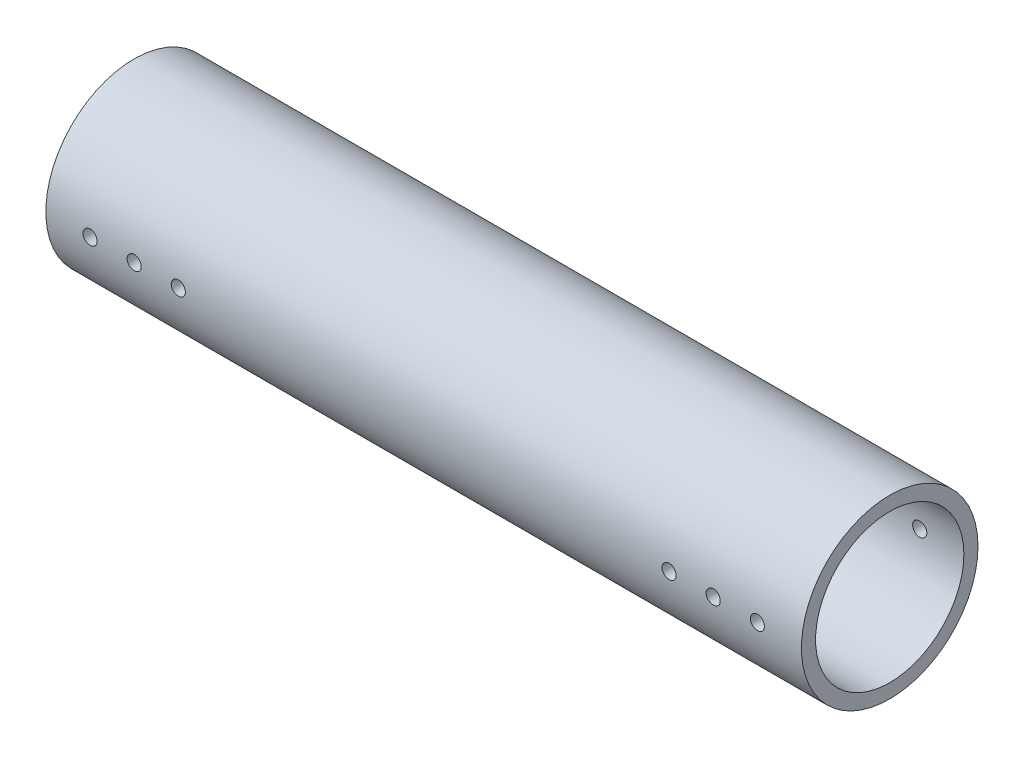
SolidWorks part; units mm, degrees
material "Zoltek Panex 33"
ref_plane "Спереди" through (0, 0, 0) normal (0, 0, 1) x (1, 0, 0)
ref_plane "Сверху" through (0, 0, 0) normal (0, 1, 0) x (1, 0, 0)
ref_plane "Справа" through (0, 0, 0) normal (1, 0, 0) x (0, 0, -1)
other "Configuration Table"
sketch "Эскиз2" plane through (0, 0, 0) normal (1, 0, 0) x (0, 0, -1)
  circle A0 centre (0, 0) radius 25
  circle A1 centre (0, 0) radius 21
  dimension "D1" = 50
  dimension "D2" = 42
extrude "Бобышка-Вытянуть2" add sketch "Эскиз2" along normal blind 214
ref_plane "Плоскость1" through (0, 0, 25) normal (0, 0, 1) x (1, 0, 0)
sketch "Эскиз4" plane through (0, 0, 25) normal (0, 0, 1) x (1, 0, 0)
  line L0 (0, -25) -> (214, -25) construction
  line L1 (214, -25) -> (214, 25) construction
  circle A0 centre (12.5, 0) radius 2
  circle A1 centre (201.5, 0) radius 2
  circle A2 centre (25, 0) radius 2
  circle A3 centre (37.5, 0) radius 2
  circle A4 centre (189, 0) radius 2
  circle A5 centre (176.5, 0) radius 2
  dimension "D1" = 4
  dimension "D4" = 4
  dimension "D6" = 4
  dimension "D8" = 4
  dimension "D10" = 4
  dimension "D11" = 4
  dimension "D2" = 12.5
  dimension "D3" = 25
  dimension "D5" = 12.5
  dimension "D7" = 12.5
  dimension "D9" = 12.5
  dimension "15" = 12.5
  dimension "D12" = 12.5
extrude "Вырез-Вытянуть2" cut sketch "Эскиз4" against normal through all and the other way blind 10 contours A0 | A1 | A2 | A3 | A5 | A4
equation "\"Diameter\"= 50мм"
equation "\"D1@Эскиз2\"= \"Diameter\""
equation "\"Length\" = 214мм"
equation "\"Thickness\"= 4мм"
equation "\"D1@Бобышка-Вытянуть2\"= \"Length\""
equation "\"D2@Эскиз2\" = \"Diameter\" - \"Thickness\" * 2"
equation "\"D4@Эскиз4\"=\"D1@Эскиз4\""
equation "\"D5@Эскиз4\"=\"D2@Эскиз4\""
equation "\"D3@Эскиз4\"=\"Diameter\"/2"
equation "\"D6@Эскиз4\"=\"D1@Эскиз4\""
equation "\"D8@Эскиз4\"=\"D6@Эскиз4\""
equation "\"D10@Эскиз4\"=\"D4@Эскиз4\""
equation "\"D11@Эскиз4\"=\"D4@Эскиз4\""
equation "\"D9@Эскиз4\"=\"D7@Эскиз4\""
